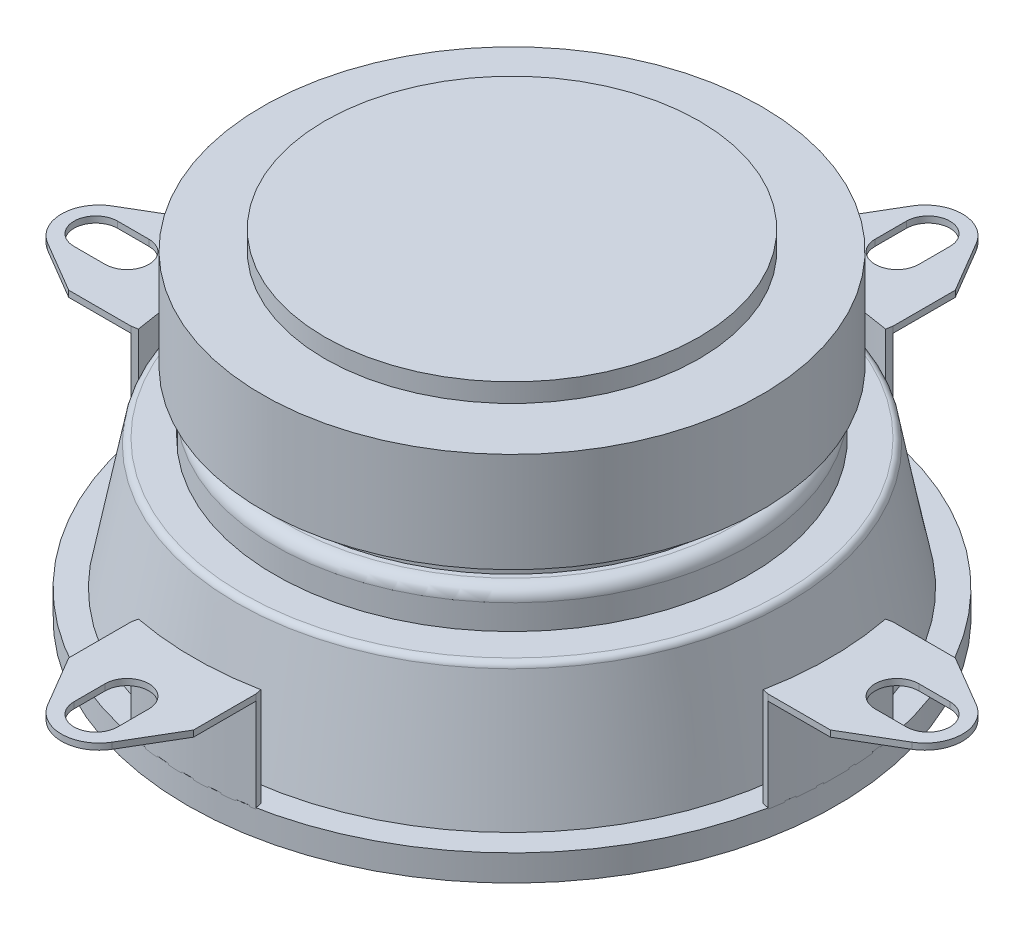
SolidWorks part; units mm, degrees
ref_plane "Спереди" through (0, 0, 0) normal (0, 0, 1) x (1, 0, 0)
ref_plane "Сверху" through (0, 0, 0) normal (0, 1, 0) x (1, 0, 0)
ref_plane "Справа" through (0, 0, 0) normal (1, 0, 0) x (0, 0, -1)
sketch "Sketch1" plane through (0, 0, 0) normal (0, 1, 0) x (1, 0, 0)
  circle A0 centre (0, 0) radius 26
  dimension "D1" = 52
sketch "Sketch2" plane through (0, 0, 0) normal (0, 0, 1) x (1, 0, 0)
  line L0 (26, 0) -> (26, 2.0944)
  line L1 (26, 0) -> (-26, 0) construction
  line L2 (26, 2.0944) -> (24, 2.0944)
  line L3 (24, 2.0944) -> (22.078, 12.0944)
  line L4 (21.587, 12.5) -> (19, 12.5)
  line L5 (19, 12.5) -> (19, 14.5)
  line L6 (18, 15.5) -> (17.6179, 15.5)
  line L7 (17.6179, 15.5) -> (17.6179, 17.5)
  line L8 (17.6179, 17.5) -> (20, 17.5)
  line L9 (20, 17.5) -> (20, 25.5)
  line L10 (20, 25.5) -> (15, 25.5)
  line L11 (15, 25.5) -> (15, 27)
  line L12 (15, 27) -> (0, 27)
  line L13 (0, 27) -> (0, 0)
  line L14 (0, 0) -> (26, 0)
  line L15 (0, 0) -> (0, 24.0665) construction
  arc A0 (19, 14.5) -> (18, 15.5) centre (18, 14.5) ccw
  arc A1 (22.078, 12.0944) -> (21.587, 12.5) centre (21.587, 12) ccw
  point P25 (22, 12.5)
  dimension "D7" = 1
  dimension "D12" = 0.5
  dimension "D1" = 40
  dimension "D2" = 8
  dimension "D3" = 1.5
  dimension "D4" = 27
  dimension "D5" = 2
  dimension "D6" = 2
  dimension "D8" = 2
  dimension "D9" = 3
  dimension "D10" = 3
  dimension "D11" = 2
  dimension "D13" = 10
  dimension "D14" = 5
revolve "Revolve1" add sketch "Sketch2" angle 360 about L15
sketch "Sketch3" plane through (0, 0, 0) normal (0, 0, 1) x (1, 0, 0)
  line L0 (21.1894, 3.0167) -> (23.0081, 3.0167)
  line L1 (23.0081, 3.0167) -> (23.5879, 0)
  line L2 (26, 0) -> (-26, 0) construction
  line L3 (24, 2.0944) -> (22.078, 12.0944) construction
  line L4 (0, 0) -> (0, 10.1569) construction
  line L5 (0, 4.9596) -> (-3.757, 4.9596) construction
  line L6 (23.5879, 0) -> (23.5879, -1.3699)
  line L7 (23.5879, -1.3699) -> (0, -1.0054)
  line L8 (0, -1.0054) -> (0, 4.9596)
  arc A0 (21.1894, 3.0167) -> (16.2656, 2.1678) centre (18.7434, 2.5) cw
  arc A1 (16.2656, 2.1678) -> (0, 4.9596) centre (0, -43.8191) ccw
  dimension "D2" = 2.5
  dimension "D1" = 0.8
revolve "Cut-Revolve1" cut sketch "Sketch3" angle 360 about L4
sketch "Sketch4" plane through (0, 0, 0) normal (0, 1, 0) x (1, 0, 0)
  line L0 (0, 0) -> (0, -39.6528) construction
  line L1 (-5, -25.5147) -> (-5, -30.5147)
  line L2 (-5, -30.5147) -> (-2.5847, -34.6137)
  line L3 (5, -25.5147) -> (5, -30.5147)
  line L4 (5, -30.5147) -> (2.5847, -34.6137)
  arc A0 (-5, -25.5147) -> (5, -25.5147) centre (0, 0) ccw
  circle A2 centre (0, 0) radius 26 construction
  arc A3 (-2.5847, -34.6137) -> (2.5847, -34.6137) centre (0, -33.0907) ccw
  point P13 (0, -39)
  dimension "D4" = 3
  dimension "D5" = 10.0907
  dimension "D1" = 10
  dimension "D2" = 13
  dimension "D3" = 5
extrude "Boss-Extrude1" add sketch "Sketch4" against normal blind 0.5 from offset 10 separate body
sketch "Sketch5" plane through (0, 10, 0) normal (0, 1, 0) x (-1, 0, 0)
  arc A0 (5, 25.5147) -> (-5, 25.5147) centre (0, 0) ccw construction
  arc A1 (5, 25.5147) -> (-5, 25.5147) centre (0, 0) ccw
extrude "Extrude-Thin1" add sketch "Sketch5" against normal blind 8 thin thin type one direction reverse wall 0.5
sketch "Sketch6" plane through (0, 10, 0) normal (0, 1, 0) x (-1, 0, 0)
  line L0 (0, 0) -> (0, 36.0907) construction
  line L1 (0, 30.8407) -> (0, 33.3407) construction
  line L2 (-1.75, 30.8407) -> (-1.75, 33.3407)
  line L3 (1.75, 30.8407) -> (1.75, 33.3407)
  arc A1 (-1.75, 30.8407) -> (1.75, 30.8407) centre (0, 30.8407) ccw
  arc A2 (1.75, 33.3407) -> (-1.75, 33.3407) centre (0, 33.3407) ccw
  arc A3 (2.5847, 34.6137) -> (-2.5847, 34.6137) centre (0, 33.0907) ccw construction
  point P3 (0, 32.0907)
  dimension "D2" = 1
  dimension "D3" = 6
  dimension "D1" = 3.5
extrude "Cut-Extrude1" cut sketch "Sketch6" against normal blind 9
pattern_circular "CirPattern2" count 4 over 360 about axis through (0, 2.1678, 0) along (0, -1, 0) of bodies 105
ref_plane "Plane1" through (0, 0, 0) normal (-0.7071, 0, 0.7071) x (0.7071, 0, 0.7071)
sketch "Sketch7" plane through (0, 0, 0) normal (0, 1, 0) x (1, 0, 0)
  line L0 (26.8449, 26.8449) -> (-26.8449, -26.8449) construction
  line L1 (0, 0) -> (0, 11.1954) construction
  point P2 (0, 0)
  dimension "D1" = 45
ref_plane "Plane2" through (0, 0, 0) normal (-0.7071, 0, -0.7071) x (-0.7071, 0, 0.7071)
